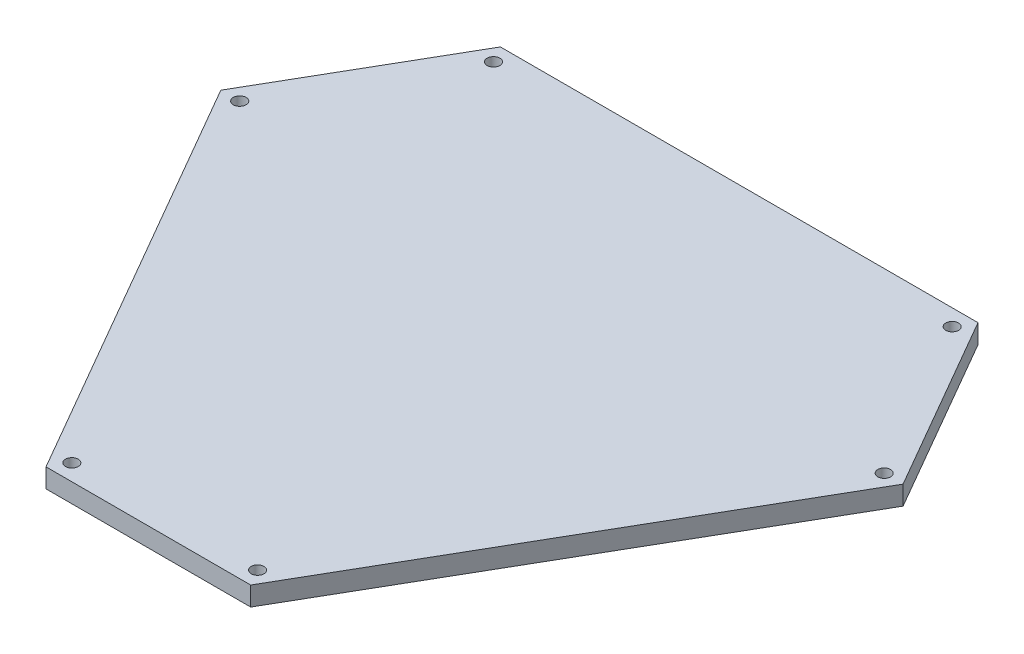
SolidWorks part; units mm, degrees
ref_plane "Front Plane" through (0, 0, 0) normal (0, 0, 1) x (1, 0, 0)
ref_plane "Top Plane" through (0, 0, 0) normal (0, 1, 0) x (1, 0, 0)
ref_plane "Right Plane" through (0, 0, 0) normal (1, 0, 0) x (0, 0, -1)
sketch "Sketch1" plane through (0, 0, 0) normal (0, 1, 0) x (1, 0, 0)
  line L0 (-106.25, 61.3435) -> (81.25, -46.9097) construction
  line L1 (87.5, 93.8194) -> (-87.5, 93.8194)
  line L2 (-87.5, 93.8194) -> (-125, 28.8675)
  line L3 (-125, 28.8675) -> (-37.5, -122.6869)
  line L4 (-37.5, -122.6869) -> (37.5, -122.6869)
  line L5 (37.5, -122.6869) -> (125, 28.8675)
  line L6 (125, 28.8675) -> (87.5, 93.8194)
  line L7 (106.25, 61.3435) -> (-81.25, -46.9097) construction
  line L8 (0, 93.8194) -> (0, -122.6869) construction
  line L9 (87.5, 93.8194) -> (-37.5, -122.6869) construction
  line L10 (-87.5, 93.8194) -> (37.5, -122.6869) construction
  line L11 (125, 28.8675) -> (-125, 28.8675) construction
  point P8 (0, 0)
  dimension "D1" = 175
  dimension "D2" = 75
  dimension "D3" = 120
extrude "Boss-Extrude1" add sketch "Sketch1" along normal blind 7
sketch "Sketch2" plane through (0, 7, 0) normal (0, 1, 0) x (1, 0, 0)
  circle A0 centre (118.0718, 28.8675) radius 2.35
  circle A1 centre (84.0359, 87.8194) radius 2.35
  circle A2 centre (-84.0359, 87.8194) radius 2.35
  circle A3 centre (-118.0718, 28.8675) radius 2.35
  circle A4 centre (-34.0359, -116.6869) radius 2.35
  circle A5 centre (34.0359, -116.6869) radius 2.35
  circle A6 centre (34.0359, -116.6869) radius 1.7 construction
  circle A9 centre (-34.0359, -116.6869) radius 1.7 construction
  circle A10 centre (-118.0718, 28.8675) radius 1.7 construction
  circle A11 centre (-84.0359, 87.8194) radius 1.7 construction
  circle A12 centre (118.0718, 28.8675) radius 1.7 construction
  circle A13 centre (84.0359, 87.8194) radius 1.7 construction
  point P12 (0, 0)
  point P13 (0, 0)
  dimension "D1" = 4.7
extrude "Cut-Extrude1" cut sketch "Sketch2" against normal blind 4
